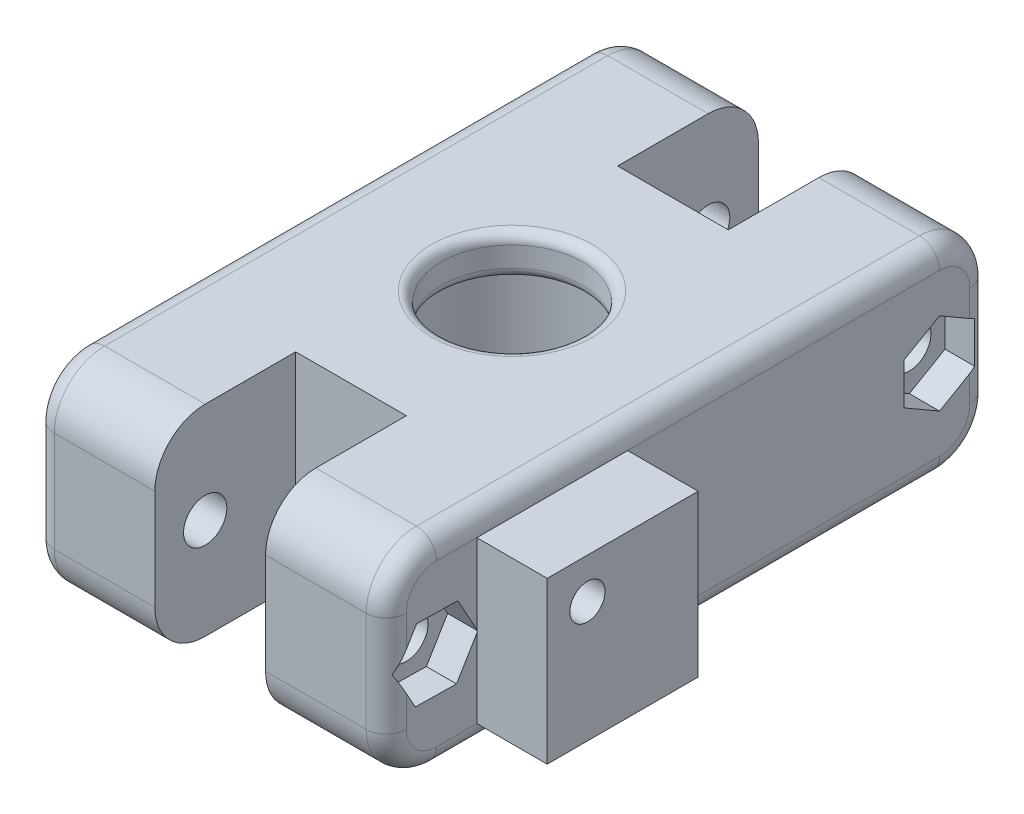
SolidWorks part; units mm, degrees
ref_plane "Front Plane" through (0, 0, 0) normal (0, 0, 1) x (1, 0, 0)
ref_plane "Top Plane" through (0, 0, 0) normal (0, 1, 0) x (1, 0, 0)
ref_plane "Right Plane" through (0, 0, 0) normal (1, 0, 0) x (0, 0, -1)
sketch "Sketch1" plane through (0, 0, 0) normal (0, 1, 0) x (1, 0, 0)
  line L1 (14.8917, -26.7815) -> (-20.1083, -26.7815)
  line L2 (14.8917, -26.7815) -> (14.8917, 33.2185)
  line L3 (14.8917, 33.2185) -> (-20.1083, 33.2185)
  line L4 (-20.1083, -26.7815) -> (-20.1083, 33.2185)
  dimension "D1" = 35
  dimension "D2" = 60
extrude "Boss-Extrude1" add sketch "Sketch1" along normal blind 20
sketch "Sketch2" plane through (0, 0, 0) normal (0, -1, 0) x (1, 0, 0)
  line L0 (-20.1083, 26.7815) -> (14.8917, 26.7815) construction
  line L1 (-20.1083, -33.2185) -> (-20.1083, 26.7815) construction
  circle A0 centre (-2.6083, -3.2185) radius 10
  dimension "D1" = 20
  dimension "D2" = 30
  dimension "D3" = 17.5
extrude "Cut-Extrude1" cut sketch "Sketch2" against normal blind 16
sketch "Sketch4" plane through (0, 16, 0) normal (0, -1, 0) x (1, 0, 0)
  line L0 (-20.1083, -33.2185) -> (-20.1083, 26.7815) construction
  line L2 (-20.1083, 26.7815) -> (14.8917, 26.7815) construction
  line L3 (14.8917, -33.2185) -> (-20.1083, -33.2185) construction
  circle A0 centre (-2.6083, -3.2185) radius 7
  dimension "D1" = 14
  dimension "D2" = 17.5
  dimension "D3" = 30
  dimension "D4" = 30
extrude "Cut-Extrude2" cut sketch "Sketch4" against normal through all
fillet "Fillet1" radius 2 8 edges at (-20.1083, 10, -33.2185) (-20.1083, 20, -3.2185) (-20.1083, 10, 26.7815) (-20.1083, 0, -3.2185) (14.8917, 10, 26.7815) (14.8917, 20, -3.2185) (14.8917, 10, -33.2185) (14.8917, 0, -3.2185)
sketch "Sketch5" plane through (0, 0, 0) normal (0, -1, 0) x (1, 0, 0)
  line L0 (-18.1083, 26.7815) -> (12.8917, 26.7815) construction
  line L1 (-8.1083, 26.7815) -> (2.8917, 26.7815)
  line L2 (-8.1083, 26.7815) -> (-8.1083, 12.7815)
  line L3 (-8.1083, 12.7815) -> (2.8917, 12.7815)
  line L4 (2.8917, 26.7815) -> (2.8917, 12.7815)
  line L5 (12.8917, -33.2185) -> (-18.1083, -33.2185) construction
  line L6 (2.8917, -33.2185) -> (-8.1083, -33.2185)
  line L7 (2.8917, -33.2185) -> (2.8917, -19.2185)
  line L8 (2.8917, -19.2185) -> (-8.1083, -19.2185)
  line L9 (-8.1083, -33.2185) -> (-8.1083, -19.2185)
  line L10 (-20.1083, -31.2185) -> (-20.1083, 24.7815) construction
  line L11 (14.8917, 24.7815) -> (14.8917, -31.2185) construction
  dimension "D1" = 11
  dimension "D2" = 11
  dimension "D3" = 12
  dimension "D4" = 12
  dimension "D5" = 12
  dimension "D6" = 14
  dimension "D7" = 14
extrude "Cut-Extrude3" cut sketch "Sketch5" against normal through all
sketch "Sketch6" plane through (-20.1083, 0, 0) normal (-1, 0, 0) x (0, 0, 1)
  line L0 (-33.2185, 20) -> (26.7815, 20) construction
  line L2 (-33.2185, 0) -> (-33.2185, 20) construction
  line L3 (26.7815, 20) -> (26.7815, 0) construction
  circle A0 centre (-28.2185, 10) radius 2.15
  circle A1 centre (21.7815, 10) radius 2.15
  dimension "D1" = 4.3
  dimension "D2" = 4.3
  dimension "D3" = 50
  dimension "D4" = 0
  dimension "D5" = 10
  dimension "D6" = 5
  dimension "D7" = 5
extrude "Cut-Extrude4" cut sketch "Sketch6" against normal through all
fillet "Fillet3" radius 5 8 edges at (-19.5225, 0.5858, 26.1957) (-19.5225, 19.4142, 26.1957) (14.3059, 19.4142, 26.1957) (14.3059, 0.5858, 26.1957) (7.8917, 0, 26.7815) (7.8917, 20, 26.7815) (-13.1083, 20, 26.7815) (-13.1083, 0, 26.7815)
fillet "Fillet4" radius 5 8 edges at (-19.5225, 0.5858, -32.6327) (14.3059, 0.5858, -32.6327) (14.3059, 19.4142, -32.6327) (-19.5225, 19.4142, -32.6327) (-13.1083, 20, -33.2185) (7.8917, 20, -33.2185) (7.8917, 0, -33.2185) (-13.1083, 0, -33.2185)
fillet "Fillet7" radius 1 2 edges at (-2.6083, 16, -10.2185) (-2.6083, 20, -10.2185)
sketch "Sketch9" plane through (14.8917, 0, 0) normal (1, 0, 0) x (0, 0, -1)
  line L0 (28.2185, 18) -> (-21.7815, 18) construction
  line L1 (-17.7815, 18) -> (-2.7815, 18)
  line L2 (-17.7815, 18) -> (-17.7815, 2)
  line L3 (-17.7815, 2) -> (-2.7815, 2)
  line L4 (-2.7815, 18) -> (-2.7815, 2)
  line L5 (-21.7815, 2) -> (28.2185, 2) construction
  line L7 (-24.7815, 15) -> (-24.7815, 5) construction
  dimension "D1" = 15
  dimension "D2" = 7
extrude "Boss-Extrude3" add sketch "Sketch9" along normal blind 7
sketch "Sketch10" plane through (21.8917, 0, 0) normal (1, 0, 0) x (0, 0, -1)
  line L7 (-2.7815, 18) -> (-17.7815, 18) construction
  line L8 (-17.7815, 18) -> (-17.7815, 2) construction
  circle A0 centre (-13.7815, 14) radius 1.75
  dimension "D1" = 4
  dimension "D2" = 4
  dimension "D3" = 3.5
extrude "Cut-Extrude6" cut sketch "Sketch10" against normal blind 5
sketch "Sketch12" plane through (-20.1083, 0, 0) normal (-1, 0, 0) x (0, 0, 1)
  circle A0 centre (-28.2185, 10) radius 3.6
  circle A1 centre (21.7815, 10) radius 3.6
  dimension "D1" = 7.2
  dimension "D2" = 7.2
extrude "Cut-Extrude7" cut sketch "Sketch12" against normal blind 4
sketch "Sketch13" plane through (14.8917, 0, 0) normal (1, 0, 0) x (0, 0, -1)
  line L1 (-19.794, 6.4149) -> (-17.6829, 9.9287)
  line L2 (-17.6829, 9.9287) -> (-19.6704, 13.5138)
  line L3 (-19.6704, 13.5138) -> (-23.769, 13.5851)
  line L4 (-23.769, 13.5851) -> (-25.8801, 10.0713)
  line L5 (-25.8801, 10.0713) -> (-23.8926, 6.4862)
  line L6 (-23.8926, 6.4862) -> (-19.794, 6.4149)
  line L7 (28.2185, 5.9008) -> (31.7685, 7.9504)
  line L8 (31.7685, 7.9504) -> (31.7685, 12.0496)
  line L9 (31.7685, 12.0496) -> (28.2185, 14.0992)
  line L10 (28.2185, 14.0992) -> (24.6685, 12.0496)
  line L11 (24.6685, 12.0496) -> (24.6685, 7.9504)
  line L12 (24.6685, 7.9504) -> (28.2185, 5.9008)
  circle A0 centre (-21.7815, 10) radius 3.55 construction
  circle A1 centre (28.2185, 10) radius 3.55 construction
  dimension "D1" = 7.1
  dimension "D2" = 7.1
extrude "Cut-Extrude8" cut sketch "Sketch13" against normal blind 3
